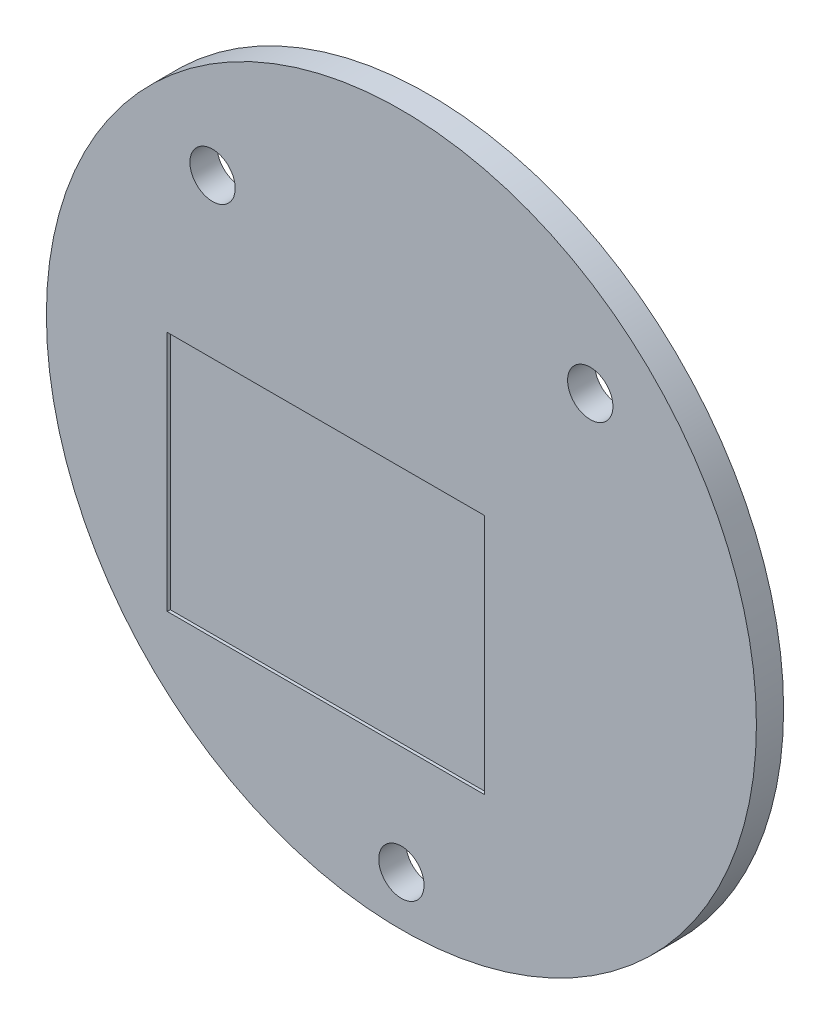
SolidWorks part; units mm, degrees
ref_plane "Alzado" through (0, 0, 0) normal (0, 0, 1) x (1, 0, 0)
ref_plane "Planta" through (0, 0, 0) normal (0, 1, 0) x (1, 0, 0)
ref_plane "Vista lateral" through (0, 0, 0) normal (1, 0, 0) x (0, 0, -1)
sketch "Croquis1" plane through (0, 0, 0) normal (0, 0, 1) x (1, 0, 0)
  line L0 (-12.5, 13.5) -> (12.5, 13.5) construction
  circle A0 centre (0, 0) radius 23.5
  circle A1 centre (0, -20.2) radius 1.5
  circle A2 centre (-12.5, 13.5) radius 1.5
  circle A3 centre (12.5, 13.5) radius 1.5
  point P5 (0, 13.5)
  point P18 (0, 0)
  dimension "D3" = 3
  dimension "D11" = 47
  dimension "D1" = 25
  dimension "D2" = 13.5
  dimension "D4" = 20.2
extrude "Saliente-Extruir1" add sketch "Croquis1" along normal blind 1.8
sketch "Croquis2" plane through (0, 0, 1.8) normal (0, 0, 1) x (1, 0, 0)
  line L0 (-14.5, -12) -> (-14.5, 2) construction
  line L1 (-14.5, -12) -> (4.5, -12) construction
  line L2 (4.5, -12) -> (4.5, 2) construction
  line L3 (-14.5, 2) -> (4.5, 2) construction
  line L4 (-3.5, -1) -> (-3.5, 1) construction
  line L5 (-3.5, -1) -> (3.5, -1) construction
  line L6 (3.5, -1) -> (3.5, 1) construction
  line L7 (-3.5, 1) -> (3.5, 1) construction
  line L8 (-3.5, -1) -> (3.5, 1) construction
  line L9 (3.5, -1) -> (-3.5, 1) construction
  line L10 (-15.5, 3) -> (5.5, 3)
  line L11 (5.5, -13) -> (5.5, 3)
  line L12 (-15.5, -13) -> (5.5, -13)
  line L13 (-15.5, -13) -> (-15.5, 3)
  dimension "D1" = 2
  dimension "D2" = 7
  dimension "D3" = 1
  dimension "D4" = 14
  dimension "D5" = 19
  dimension "D6" = 1
extrude "Cortar-Extruir1" cut sketch "Croquis2" against normal blind 0.2
